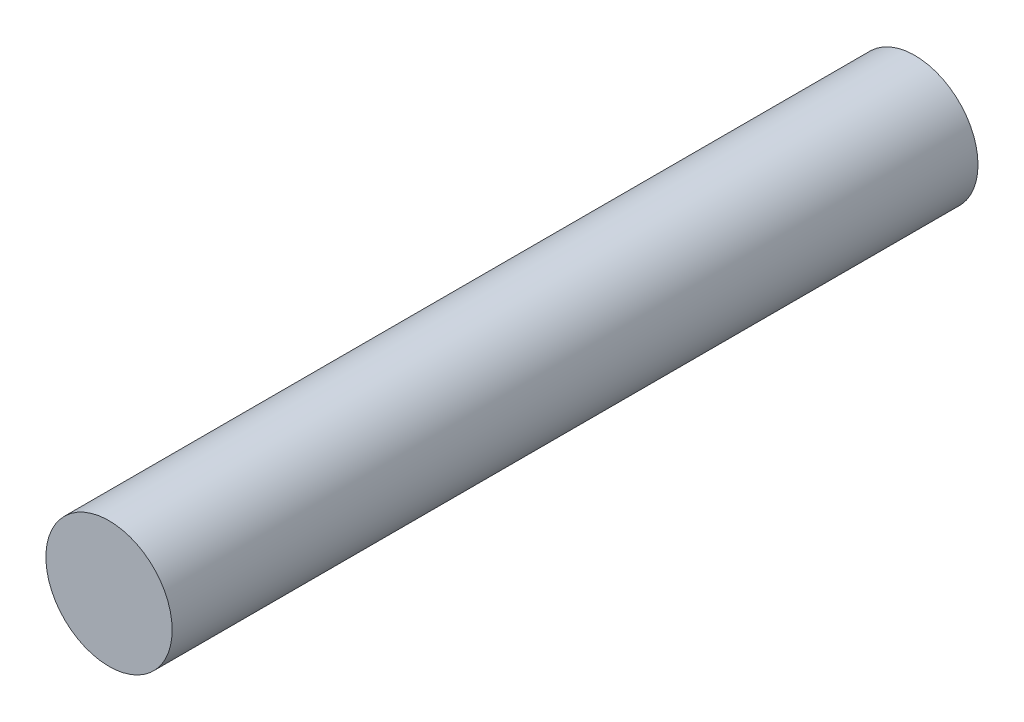
SolidWorks part; units mm, degrees
ref_plane "Front Plane" through (0, 0, 0) normal (0, 0, 1) x (1, 0, 0)
ref_plane "Top Plane" through (0, 0, 0) normal (0, 1, 0) x (1, 0, 0)
ref_plane "Right Plane" through (0, 0, 0) normal (1, 0, 0) x (0, 0, -1)
sketch "Sketch1" plane through (0, 0, 0) normal (0, 0, 1) x (1, 0, 0)
  circle A0 centre (-23.9727, -13.5789) radius 3.15
  dimension "D1" = 6.3
extrude "Boss-Extrude1" add sketch "Sketch1" along normal blind 40.2
